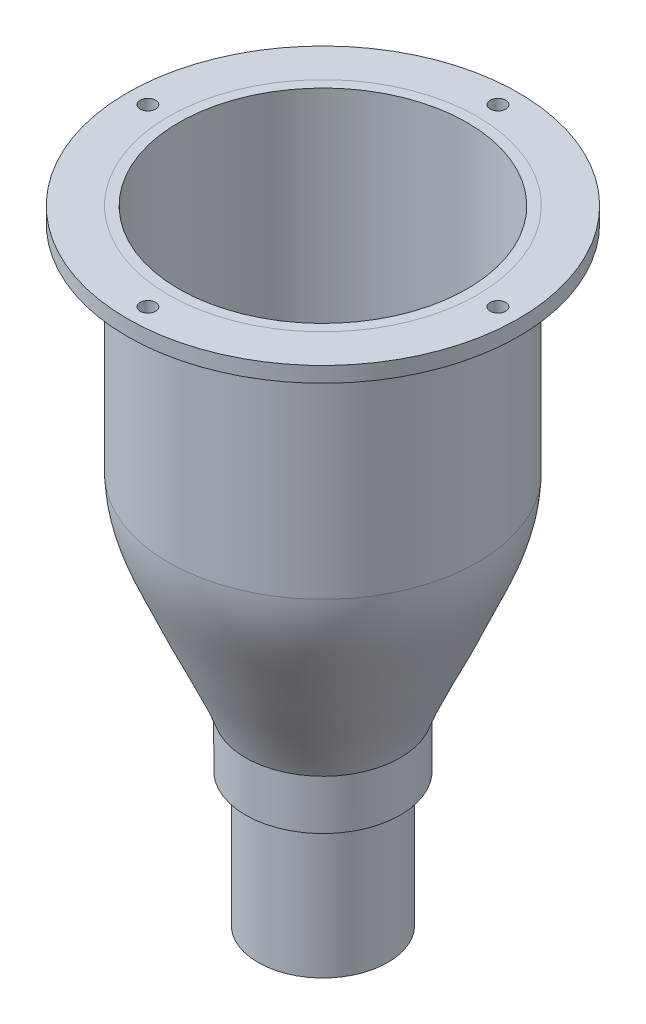
SolidWorks part; units mm, degrees
ref_plane "Płaszczyzna przednia" through (0, 0, 0) normal (0, 0, 1) x (1, 0, 0)
ref_plane "Płaszczyzna górna" through (0, 0, 0) normal (0, 1, 0) x (1, 0, 0)
ref_plane "Płaszczyzna prawa" through (0, 0, 0) normal (1, 0, 0) x (0, 0, -1)
sketch "Sketch1" plane through (0, 0, 0) normal (0, 1, 0) x (1, 0, 0)
  circle A0 centre (0, 0) radius 12.6
  circle A1 centre (0, 0) radius 11.1
  dimension "D1" = 25.2
  dimension "D2" = 1.5
extrude "Boss-Extrude1" add sketch "Sketch1" against normal blind 26
ref_plane "Plane1" through (0, 50, 0) normal (0, 1, 0) x (1, 0, 0)
sketch "Sketch2" plane through (0, 50, 0) normal (0, 1, 0) x (1, 0, 0)
  circle A0 centre (0, 0) radius 28
  circle A1 centre (0, 0) radius 30
  dimension "D1" = 56
  dimension "D2" = 2
extrude "Boss-Extrude2" add sketch "Sketch2" along normal blind 45 separate body contours A1 | A0
sketch "Sketch6" plane through (0, 0, 0) normal (1, 0, 0) x (0, 0, -1)
  line L1 (-52.0025, 57.5992) -> (47.7591, 57.5992)
  line L2 (-52.0025, 57.5992) -> (-52.0025, -12.321)
  line L3 (-52.0025, -12.321) -> (47.7591, -12.321)
  line L4 (47.7591, 57.5992) -> (47.7591, -12.321)
  line L7 (12.6, 0) -> (11.1, 0)
  line L8 (30, 50) -> (28, 50)
  line L9 (-28, 50) -> (-30, 50)
  line L10 (-28, 50) -> (-30, 50)
  line L11 (30, 50) -> (28, 50)
  line L12 (0, 0) -> (0, 60.1889) construction
  spline S0 degree 3 poles (12.6, 0) (14.219, 10.4067) (19.2179, 18.8627) (26.1184, 35.4758) (29.6864, 42.333) (30, 50) knots 0 0 0 0 0.476692 0.576692 1 1 1 1
  spline S1 degree 3 poles (11.1, 0) (11.5156, 8.4627) (16.2873, 17.4201) (23.9033, 35.0286) (26.5601, 41.7039) (28, 50) knots 0 0 0 0 0.530324 0.630324 1 1 1 1
  point P7 (0, 0)
  point P8 (11.1, 0)
  point P13 (0, 0)
  point P14 (22.9103, 27.7541)
  point P15 (21.1711, 29.3925)
  point P17 (20.9025, 28.0992)
revolve "Revolve2" add sketch "Sketch6" angle 360 about L12 region at (0, 26.2521, -20.9959)
sketch "Sketch7" plane through (0, 95, 0) normal (0, 1, 0) x (1, 0, 0)
  circle A2 centre (0, 0) radius 38
  circle A3 centre (0, 0) radius 38
  circle M2 centre (0, 0) radius 30
  dimension "D1" = 8
extrude "Boss-Extrude3" add sketch "Sketch7" against normal blind 3 separate body contours A3 M2 region at (-36.9252, 95, 0)
sketch "Sketch8" plane through (0, 0, 0) normal (0, 1, 0) x (1, 0, 0)
  circle A0 centre (0, 0) radius 15.0116
  circle A1 centre (0, 0) radius 12.6
extrude "Boss-Extrude4" add sketch "Sketch8" along normal up to surface (9.6372 mm away) contours A0 | A1 up to face at (0, 50, 30)
hole_wizard "Ø3.0 mm Dowel Holes1" positions "Sketch9" profile "Sketch10" hole size "Ø3.0" standard "ANSI Metric"
sketch "Sketch9" plane through (0, 95, 0) normal (0, 1, 0) x (1, 0, 0)
  point P0 (0, 34)
  dimension "D1" = 34
sketch "Sketch10" plane through (0, 95, -34) normal (1, 0, 0) x (0, 0, 1)
  line L0 (0, 0) -> (0, 13.4013)
  line L1 (0, 13.4013) -> (1.5, 12.5)
  line L2 (1.5, 12.5) -> (1.5, 0)
  line L5 (1.5, 0) -> (0, 0)
  line L10 (0, 13.4013) -> (-1.5, 12.5) construction
  line L11 (0, -6.35) -> (0, 107.95) construction
  dimension "Hole Dia." = 3
  dimension "Hole Depth" = 12.5
  dimension "Drill Angle" = 118
pattern_circular "CirPattern1" count 4 over 360 about axis through (0, 95, 0) along (0, -1, 0) of "Ø3.0 mm Dowel Holes1"
